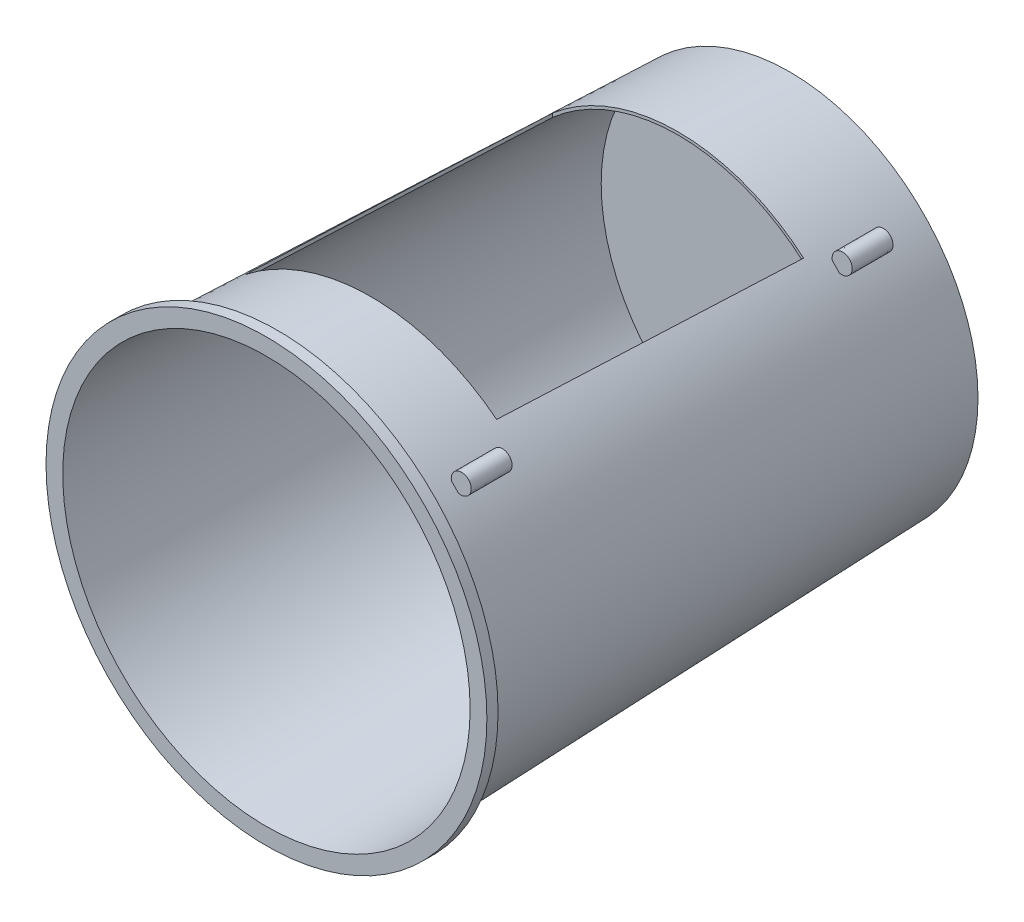
SolidWorks part; units mm, degrees
material "AISI 304"
ref_plane "Front Plane" through (0, 0, 0) normal (0, 0, 1) x (1, 0, 0)
ref_plane "Top Plane" through (0, 0, 0) normal (0, 1, 0) x (1, 0, 0)
ref_plane "Right Plane" through (0, 0, 0) normal (1, 0, 0) x (0, 0, -1)
sketch "Pail_Base_Profile" plane through (0, 0, 0) normal (0, 0, 1) x (1, 0, 0)
  circle A0 centre (0, 0) radius 135
  dimension "D1" = 270
extrude "Tapered_Pail_Blank" add sketch "Pail_Base_Profile" along normal blind 375 draft 1.985 from offset 190 draft outward yes offset against normal yes
shell "Pail_Wall_2mm" thickness 2 removed face at (148, 0, 185)
sketch "Pail_Rim_Profile" plane through (0, 0, 0) normal (0, 0, 1) x (1, 0, 0)
  circle A0 centre (0, 0) radius 158
  circle A1 centre (0, 0) radius 146
  dimension "D1" = 292
  dimension "D2" = 316
extrude "Pail_Reinforced_Rim" add sketch "Pail_Rim_Profile" along normal blind 8 from offset 177
sketch "Loading_Opening_Profile" plane through (0, 0, 0) normal (1, 0, 0) x (0, 0, -1)
  line L0 (-110, 0) -> (110, 0)
  line L1 (110, 0) -> (110, 250)
  line L2 (110, 250) -> (-110, 250)
  line L3 (-110, 250) -> (-110, 0)
  dimension "Half_Opening_Length" = 110
  dimension "Half_Opening_Length_2" = 110
  dimension "D3" = 250
extrude "Top_Loading_Opening" cut sketch "Loading_Opening_Profile" against normal mid plane 180
ref_axis "Drum_Rotation_Axis" through (0, 0, -208.75) along (0, 0, 1)
ref_plane "Lid_Hinge_Plane" through (0, 0, 0) normal (0.6975, -0.7166, 0) x (0, 0, 1)
sketch "Drum_Hinge_Knuckle_Profile" plane through (0, 0, 0) normal (0.6975, -0.7166, 0) x (0, 0, 1)
  line L0 (-169.9991, -141.6679) -> (169.9999, -153.4835) construction
  line L1 (-155, -142.2137) -> (-125.0001, -143.2558)
  line L2 (-125.0001, -143.2558) -> (-125.2431, -150.2511)
  line L3 (-125.2431, -150.2511) -> (-155.243, -149.209)
  line L4 (-155.243, -149.209) -> (-155, -142.2137)
  line L5 (125, -151.9203) -> (154.9999, -152.9624)
  line L6 (154.9999, -152.9624) -> (154.7569, -159.9578)
  line L7 (154.7569, -159.9578) -> (124.757, -158.9156)
  line L8 (124.757, -158.9156) -> (125, -151.9203)
  dimension "D1" = 124.757
  dimension "D2" = 125
  dimension "D3" = 154.7569
  dimension "D4" = 125.0001
  dimension "D5" = 125.2431
  dimension "D6" = 142.2137
  dimension "D7" = 143.2558
  dimension "D8" = 151.9203
revolve "Drum_Hinge_Knuckles" add sketch "Drum_Hinge_Knuckle_Profile" angle 360 about L0
ref_axis "Hinge_Axis" through (101.5218, 98.8084, -169.9991) along (0.0249, 0.0242, 0.9994)
ref_plane "Hinge_Datum_Plane" through (101.5218, 98.8084, -169.9991) normal (0.0249, 0.0242, 0.9994) x (0.9997, -0.0006, -0.0249)
ref_plane "Rim_Top_Plane" through (0, 0, 185) normal (0, 0, 1) x (1, 0, 0)
ref_plane "Pail_Base_Plane" through (0, 0, -190) normal (0, 0, 1) x (1, 0, 0)
